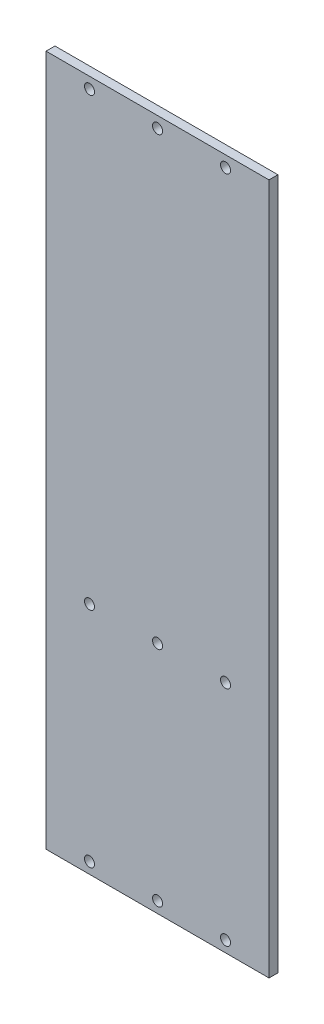
SolidWorks part; units mm, degrees
ref_plane "Piano frontale" through (0, 0, 0) normal (0, 0, 1) x (1, 0, 0)
ref_plane "Piano superiore" through (0, 0, 0) normal (0, 1, 0) x (1, 0, 0)
ref_plane "Piano destro" through (0, 0, 0) normal (1, 0, 0) x (0, 0, -1)
sketch "Schizzo1" plane through (0, 0, 0) normal (0, 0, 1) x (1, 0, 0)
  line L0 (50, 0) -> (50, 310) construction
  line L1 (0, 0) -> (100, 0)
  line L2 (0, 0) -> (0, 310)
  line L3 (0, 310) -> (100, 310)
  line L4 (100, 0) -> (100, 310)
  line L5 (0, 105) -> (100, 105) construction
  line L6 (100, 5) -> (0, 5) construction
  line L9 (100, 155) -> (0, 155) construction
  circle A0 centre (80.5, 5) radius 2.25
  circle A1 centre (50, 5) radius 2.25
  circle A2 centre (19.5, 5) radius 2.25
  circle A3 centre (19.5, 305) radius 2.25
  circle A4 centre (50, 305) radius 2.25
  circle A5 centre (80.5, 305) radius 2.25
  circle A10 centre (50, 105) radius 2.25
  circle A11 centre (80.5, 105) radius 2.25
  circle A12 centre (19.5, 105) radius 2.25
  dimension "D4" = 4.5
  dimension "D1" = 100
  dimension "D2" = 310
  dimension "D3" = 5
  dimension "D5" = 30.5
  dimension "D12" = 30.5
  dimension "D13" = 30.5
  dimension "D14" = 105
  dimension "D15" = 5
extrude "Estrusione-Estrusione1" add sketch "Schizzo1" against normal blind 4
